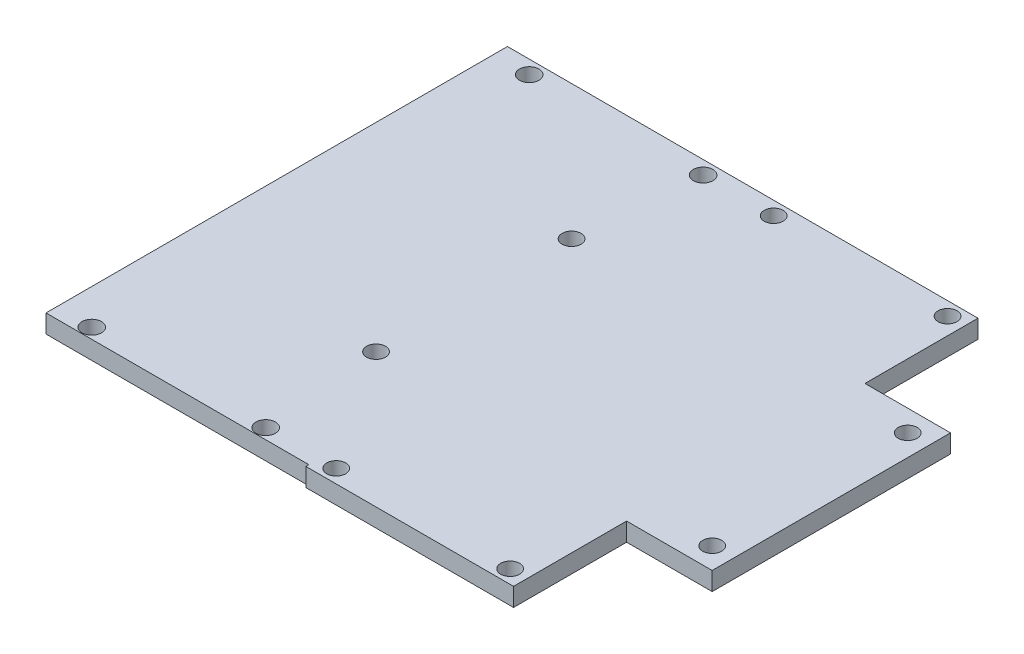
SolidWorks part; units mm, degrees
material "Thornel Mat VMA"
ref_plane "前视基准面" through (0, 0, 0) normal (0, 0, 1) x (1, 0, 0)
ref_plane "上视基准面" through (0, 0, 0) normal (0, 1, 0) x (1, 0, 0)
ref_plane "右视基准面" through (0, 0, 0) normal (1, 0, 0) x (0, 0, -1)
sketch "草图1" plane through (0, 0, 0) normal (0, 1, 0) x (1, 0, 0)
  line L1 (-31, 19.5) -> (31, 19.5)
  line L2 (-31, 19.5) -> (-31, -19.5)
  line L3 (-31, -19.5) -> (31, -19.5)
  line L4 (31, 19.5) -> (31, -19.5)
  line L5 (-31, 19.5) -> (31, -19.5) construction
  line L6 (-31, -19.5) -> (31, 19.5) construction
  line L7 (-27.5, 16) -> (27.5, 16) construction
  line L8 (-27.5, 16) -> (-27.5, -16) construction
  line L9 (-27.5, -16) -> (27.5, -16) construction
  line L10 (27.5, 16) -> (27.5, -16) construction
  line L11 (-27.5, 16) -> (27.5, -16) construction
  line L12 (-27.5, -16) -> (27.5, 16) construction
  line L13 (-14.23, 35.79) -> (14.23, 35.79) construction
  line L14 (-14.23, 35.79) -> (-14.23, -35.79) construction
  line L15 (-14.23, -35.79) -> (14.23, -35.79) construction
  line L16 (14.23, 35.79) -> (14.23, -35.79) construction
  line L17 (-14.23, 35.79) -> (14.23, -35.79) construction
  line L18 (-14.23, -35.79) -> (14.23, 35.79) construction
  line L19 (-17, 38) -> (17, 38)
  line L20 (-17, 38) -> (-17, -38)
  line L21 (-17, -38) -> (17, -38)
  line L22 (17, 38) -> (17, -38)
  line L23 (-17, 38) -> (17, -38) construction
  line L24 (-17, -38) -> (17, 38) construction
  circle A0 centre (-27.5, 16) radius 1.55
  circle A1 centre (27.5, 16) radius 1.55
  circle A2 centre (-27.5, -16) radius 1.55
  circle A3 centre (27.5, -16) radius 1.55
  circle A4 centre (-14.23, 35.79) radius 1.55
  circle A5 centre (14.23, 35.79) radius 1.55
  circle A6 centre (14.23, -35.79) radius 1.55
  circle A7 centre (-14.23, -35.79) radius 1.55
  point P0 (0, 0)
  point P6 (0, 0)
  point P15 (0, 0)
  point P20 (0, 0)
  dimension "D5" = 3.1
  dimension "D6" = 3.1
  dimension "D7" = 3.1
  dimension "D8" = 3.1
  dimension "D11" = 3.1
  dimension "D12" = 3.1
  dimension "D13" = 3.1
  dimension "D14" = 3.1
  dimension "D1" = 39
  dimension "D2" = 62
  dimension "D3" = 32
  dimension "D4" = 55
  dimension "D9" = 28.46
  dimension "D10" = 71.58
  dimension "D15" = 34
  dimension "D16" = 76
extrude "凸台-拉伸1" add sketch "草图1" along normal blind 3 contours L22 L19 L20 L1 A5 A4 | L22 L1 L20 L3 | L20 L1 L2 L3 A2 A0 | L22 L3 L20 L21 A7 A6 | L1 L22 L3 L4 A3 A1 region at (-23.9005, 0, 0) region at (0, 0, -28.5769) region at (0, 0, 0) region at (23.9005, 0, 0) region at (0, 0, 28.5769)
fillet "圆角1" [suppressed] radius 2
sketch "草图3" plane through (0, 3, 0) normal (0, 1, 0) x (1, 0, 0)
  line L0 (-17, 38) -> (-60, 38)
  line L1 (-17, 38) -> (17, 38) construction
  line L2 (-17, 38) -> (-17, 19.5) construction
  line L3 (-60, 38) -> (-60, -37.5067)
  line L4 (-60, -37.5067) -> (-1.4278, -37.5067)
  line L6 (-54.23, 35.79) -> (-25.77, 35.79) construction
  line L7 (-54.23, 35.79) -> (-54.23, -35.79) construction
  line L8 (-54.23, -35.79) -> (-25.77, -35.79) construction
  line L9 (-25.77, 35.79) -> (-25.77, -35.79) construction
  line L10 (-54.23, 35.79) -> (-25.77, -35.79) construction
  line L11 (-54.23, -35.79) -> (-25.77, 35.79) construction
  circle A0 centre (-54.23, 35.79) radius 1.6
  circle A1 centre (-25.77, 35.79) radius 1.6
  circle A2 centre (-54.23, -35.79) radius 1.6
  circle A3 centre (-25.77, -35.79) radius 1.6
  point P8 (-40, 0)
  line M6 (-17, 38) -> (-17, 19.5)
  line M7 (-17, 19.5) -> (-31, 19.5)
  line M8 (-31, 19.5) -> (-31, -19.5)
  line M9 (-31, -19.5) -> (-17, -19.5)
  line M10 (-17, -19.5) -> (-17, -38)
  dimension "D6" = 3.2
  dimension "D7" = 3.2
  dimension "D8" = 3.2
  dimension "D9" = 3.2
  dimension "D1" = 71.58
  dimension "D2" = 28.46
  dimension "D3" = 0
  dimension "D4" = 40
  dimension "D5" = 60
extrude "凸台-拉伸2" add sketch "草图3" against normal up to surface (3 mm away) contours L3 L4 L0 A3 A2 A1 A0 M10 M9 M8 M7 M6 region at (-41.4486, 3, -0.3001) up to face at (14.23, 0, -34.24)
